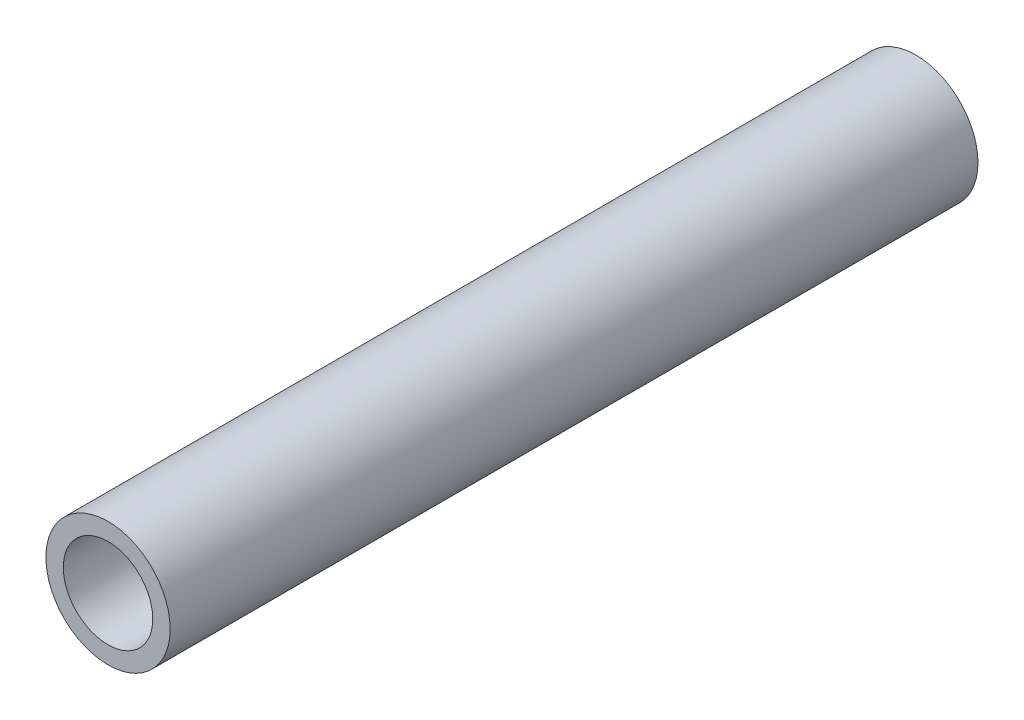
SolidWorks part; units mm, degrees
ref_plane "Front" through (0, 0, 0) normal (0, 0, 1) x (1, 0, 0)
ref_plane "Top" through (0, 0, 0) normal (0, 1, 0) x (1, 0, 0)
ref_plane "Right" through (0, 0, 0) normal (1, 0, 0) x (0, 0, -1)
sketch "Sketch1" plane through (0, 0, 0) normal (0, 0, 1) x (1, 0, 0)
  line L0 (-3.175, 0) -> (3.175, 0) construction
  line L1 (0, -3.175) -> (0, 3.175) construction
  circle A0 centre (0, 0) radius 3.175
  circle A1 centre (0, 0) radius 2.286
  point P4 (0, 0)
  point P8 (0, 0)
  point P9 (2.286, 0)
  dimension "D3" = 4.572
  dimension "D1" = 6.35
  dimension "D2" = 0.889
extrude "Boss-Extrude1" add sketch "Sketch1" along normal blind 41.275
